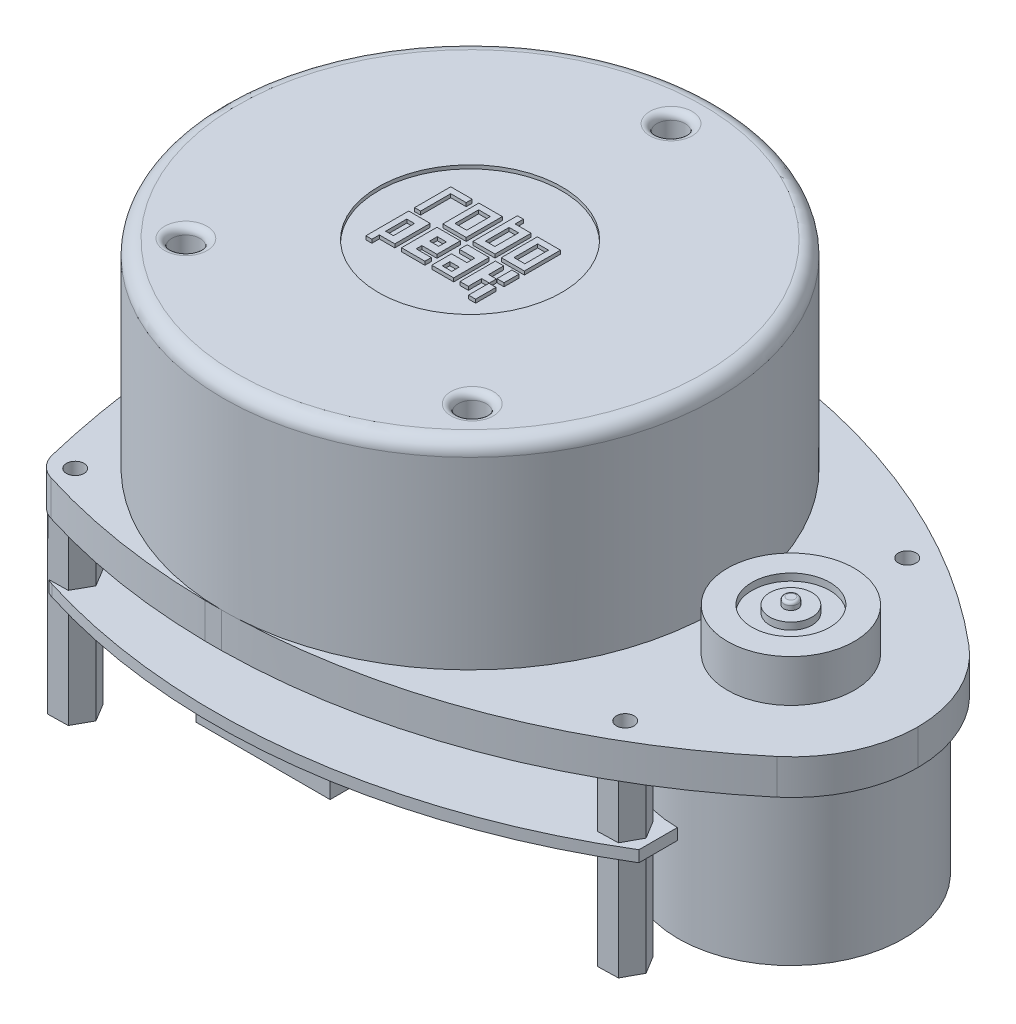
SolidWorks part; units mm, degrees
ref_plane "Спереди" through (0, 0, 0) normal (0, 0, 1) x (1, 0, 0)
ref_plane "Сверху" through (0, 0, 0) normal (0, 1, 0) x (1, 0, 0)
ref_plane "Справа" through (0, 0, 0) normal (1, 0, 0) x (0, 0, -1)
sketch "Эскиз1" plane through (0, 0, 0) normal (0, 1, 0) x (1, 0, 0)
  line L1 (-49.25, 35) -> (49.25, 35)
  line L2 (-49.25, 35) -> (-49.25, -35)
  line L3 (-49.25, -35) -> (49.25, -35)
  line L4 (49.25, 35) -> (49.25, -35)
  line L5 (-49.25, 35) -> (49.25, -35) construction
  line L6 (-49.25, -35) -> (49.25, 35) construction
  point P0 (0, 0)
  dimension "D1" = 98.5
  dimension "D2" = 70
extrude "Бобышка-Вытянуть1" add sketch "Эскиз1" along normal blind 5
sketch "Эскиз2" plane through (0, 5, 0) normal (0, 1, 0) x (1, 0, 0)
  line L0 (-49.25, 35) -> (-49.25, -35) construction
  circle A0 centre (-14.25, 0) radius 35
  point P2 (-49.25, 0)
  point P3 (-49.25, 0)
extrude "Бобышка-Вытянуть2" add sketch "Эскиз2" along normal blind 28.1
sketch "Эскиз3" plane through (0, 33.1, 0) normal (0, 1, 0) x (1, 0, 0)
  line L0 (-14.25, 0) -> (-14.25, 50000) construction
  line L1 (-14.25, -20) -> (-26.2883, -20) construction
  line L2 (-49.25, -35) -> (-14.25, -35) construction
  circle A0 centre (-14.25, 28.5) radius 2
  circle A1 centre (-34.5539, -20) radius 2
  circle A2 centre (6.0539, -20) radius 2
  arc A3 (-49.25, 0) -> (-14.25, -35) centre (-14.25, 0) ccw construction
  circle A4 centre (-14.25, 0) radius 35 construction
  dimension "D2" = 4
  dimension "D1" = 6.5
  dimension "D3" = 15
  dimension "D4" = 28.5
  dimension "D5" = 28.5
extrude "Вырез-Вытянуть1" cut sketch "Эскиз3" against normal blind 5
fillet "Скругление1" radius 2 1 edges at (-14.25, 33.1, 35)
fillet "Скругление2" radius 1 3 edges at (6.0539, 33.1, 22) (-34.5539, 33.1, 22) (-14.25, 33.1, -26.5)
sketch "Эскиз4" plane through (0, 33.1, 0) normal (0, 1, 0) x (1, 0, 0)
  line L0 (-22.1152, -6.9149) -> (-22.1152, -0.8316)
  line L1 (-22.1152, -0.8316) -> (-19.0735, -0.8316)
  line L2 (-19.0735, -0.8316) -> (-19.0735, -5.8538)
  line L3 (-19.0735, -5.8538) -> (-21.2663, -5.8538)
  line L4 (-21.2663, -5.8538) -> (-21.2663, -6.9149)
  line L5 (-21.2663, -6.9149) -> (-22.1152, -6.9149)
  line L6 (-22.1152, 0) -> (-22.1152, 5.1201)
  line L7 (-22.1152, 5.1201) -> (-19.0735, 5.1201)
  line L8 (-19.0735, 5.1201) -> (-19.0735, 4.2707)
  line L9 (-19.0735, 4.2707) -> (-21.2663, 4.2707)
  line L10 (-21.2663, 4.2707) -> (-21.2663, 0)
  line L11 (-21.2663, 0) -> (-22.1152, 0)
  line L12 (-21.2663, -1.9579) -> (-20.1699, -1.9579)
  line L13 (-20.1699, -1.9579) -> (-20.1699, -4.9509)
  line L14 (-20.1699, -4.9509) -> (-21.2663, -4.9509)
  line L15 (-21.2663, -4.9509) -> (-21.2663, -1.9579)
  line L16 (-13.8296, 0) -> (-13.8296, 6.293)
  line L17 (-18.1168, 0) -> (-14.8003, 0)
  line L18 (-18.1168, 0) -> (-18.1168, 5.1201)
  line L19 (-18.1168, 5.1201) -> (-14.8003, 5.1201)
  line L20 (-14.8003, 0) -> (-14.8003, 5.1201)
  line L21 (-9.8255, 5.1201) -> (-6.5494, 5.1201)
  line L22 (-9.8255, 5.1201) -> (-9.8255, 0)
  line L23 (-9.8255, 0) -> (-6.5494, 0)
  line L24 (-6.5494, 5.1201) -> (-6.5494, 0)
  line L25 (-8.9357, 4.2707) -> (-7.3988, 4.2707)
  line L26 (-8.9357, 4.2707) -> (-8.9357, 0.9137)
  line L27 (-8.9357, 0.9137) -> (-7.3988, 0.9137)
  line L28 (-7.3988, 4.2707) -> (-7.3988, 0.9137)
  line L29 (-17.3079, 4.2707) -> (-15.6497, 4.2707)
  line L30 (-17.3079, 4.2707) -> (-17.3079, 0.9137)
  line L31 (-17.3079, 0.9137) -> (-15.6497, 0.9137)
  line L32 (-15.6497, 4.2707) -> (-15.6497, 0.9137)
  line L33 (-12.9802, 4.2707) -> (-11.6455, 4.2707)
  line L34 (-12.9802, 4.2707) -> (-12.9802, 0.9137)
  line L35 (-12.9802, 0.9137) -> (-11.6455, 0.9137)
  line L36 (-11.6455, 4.2707) -> (-11.6455, 0.9137)
  line L37 (-12.9802, -4.142) -> (-11.6455, -4.142)
  line L38 (-12.9802, -4.142) -> (-12.9802, -5.1936)
  line L39 (-12.9802, -5.1936) -> (-11.6455, -5.1936)
  line L40 (-11.6455, -4.142) -> (-11.6455, -5.1936)
  line L41 (-16.9439, -1.9579) -> (-15.6497, -1.9579)
  line L42 (-16.9439, -1.9579) -> (-16.9439, -3.0499)
  line L43 (-16.9439, -3.0499) -> (-15.6497, -3.0499)
  line L44 (-15.6497, -1.9579) -> (-15.6497, -3.0499)
  line L46 (-7.5508, -0.7643) -> (-6.5494, -0.7643)
  line L47 (-7.5508, -0.7643) -> (-7.5508, -2.8858)
  line L48 (-7.5508, -2.8858) -> (-6.5494, -2.8858)
  line L49 (-6.5494, -0.7643) -> (-6.5494, -2.8858)
  line L50 (-6.5494, -6.9149) -> (-7.5508, -6.9149)
  line L51 (-6.5494, -6.9149) -> (-6.5494, -4.0216)
  line L52 (-6.5494, -4.0216) -> (-7.5508, -4.0216)
  line L53 (-13.8296, 6.293) -> (-12.9802, 6.293)
  line L54 (-12.9802, 6.293) -> (-12.9802, 5.1201)
  line L55 (-12.9802, 5.1201) -> (-10.7153, 5.1201)
  line L56 (-10.7153, 5.1201) -> (-10.7153, 0)
  line L57 (-10.7153, 0) -> (-13.8296, 0)
  line L58 (-9.8255, -0.8316) -> (-8.6437, -0.8316)
  line L59 (-8.6437, -0.8316) -> (-8.6437, -2.9608)
  line L60 (-8.6437, -2.9608) -> (-7.5508, -2.9608)
  line L61 (-9.8255, -0.8316) -> (-9.8255, -5.8538)
  line L62 (-9.8255, -5.8538) -> (-8.6437, -5.8538)
  line L63 (-8.6437, -5.8538) -> (-8.6437, -3.9573)
  line L64 (-8.6437, -3.9573) -> (-7.5508, -3.9573)
  line L65 (-7.5508, -2.9608) -> (-7.5508, -3.9573)
  line L66 (-13.8296, -0.8316) -> (-10.7153, -0.8316)
  line L67 (-10.7153, -0.8316) -> (-10.7153, -5.8538)
  line L68 (-10.7153, -5.8538) -> (-13.8296, -5.8538)
  line L69 (-13.8296, -5.8538) -> (-13.8296, -3.0499)
  line L70 (-13.8296, -3.0499) -> (-11.6455, -3.0499)
  line L71 (-11.6455, -3.0499) -> (-11.6455, -1.9408)
  line L72 (-11.6455, -1.9408) -> (-13.8296, -1.9408)
  line L73 (-13.8296, -1.9408) -> (-13.8296, -0.8316)
  line L74 (-18.1168, -0.8316) -> (-14.8003, -0.8316)
  line L75 (-14.8003, -0.8316) -> (-14.8003, -4.142)
  line L76 (-14.8003, -4.142) -> (-16.9439, -4.142)
  line L77 (-16.9439, -4.142) -> (-16.9439, -4.9509)
  line L78 (-16.9439, -4.9509) -> (-14.8003, -4.9509)
  line L79 (-14.8003, -4.9509) -> (-14.8003, -5.8538)
  line L80 (-14.8003, -5.8538) -> (-18.1168, -5.8538)
  line L81 (-18.1168, -5.8538) -> (-18.1168, -0.8316)
  line L82 (-7.5508, -6.9149) -> (-7.5508, -4.0216)
  circle A0 centre (-14.25, 0) radius 13
  dimension "D1" = 26
extrude "Вырез-Вытянуть3" cut sketch "Эскиз4" against normal blind 0.5 contours A0 L50 L82 L52 L51 L72 L73 L66 L67 L68 L69 L70 L71 L56 L57 L16 L53 L54 L55 L10 L11 L6 L7 L8 L9 L4 L5 L0 L1 L2 L3 L20 L17 L18 L19 L21 L24 L23 L22 L46 L49 L48 L47 | L32 L29 L30 L31 | L36 L33 L34 L35 | L28 L25 L26 L27 | L44 L41 L42 L43 | L15 L14 L13 L12 | L37 L40 L39 L38 region at (-20.7181, 33.1, 3.4544) region at (-8.1672, 33.1, -2.5922) region at (-16.4788, 33.1, -2.5922) region at (-12.3129, 33.1, -2.5922) region at (-16.2968, 33.1, 2.5039) region at (-14.2871, 33.1, -0.0991)
sketch "Эскиз5" plane through (0, 5, 0) normal (0, 1, 0) x (1, 0, 0)
  line L0 (-42.25, 30.7255) -> (-42.25, -39.5827) construction
  line L1 (27.75, 26.9972) -> (27.75, -49973.0028) construction
  line L2 (-49.25, 0) -> (49950.75, 0) construction
  circle A0 centre (-14.25, 0) radius 33 construction
  circle A1 centre (-42.25, 28) radius 1.25
  circle A2 centre (27.75, 20) radius 1.25
  circle A3 centre (27.75, -20) radius 1.25
  circle A4 centre (-42.25, -28) radius 1.25
  point P4 (-14.25, 33)
  dimension "D1" = 28
  dimension "D3" = 2.5
  dimension "D2" = 42
  dimension "D4" = 28
  dimension "D5" = 20
extrude "Вырез-Вытянуть4" cut sketch "Эскиз5" against normal blind 5
sketch "Эскиз6" plane through (0, 5, 0) normal (0, 1, 0) x (1, 0, 0)
  line L0 (49.25, 0) -> (50049.25, 0) construction
  line L1 (49.25, -35) -> (49.25, 35) construction
  circle A0 centre (31.25, 0) radius 9
  arc A1 (-14.25, -35) -> (-14.25, 35) centre (-14.25, 0) ccw construction
  point P4 (49.25, 0)
  dimension "D1" = 18
  dimension "D2" = 45.5
extrude "Бобышка-Вытянуть3" add sketch "Эскиз6" along normal blind 7
sketch "Эскиз7" plane through (0, 12, 0) normal (0, 1, 0) x (1, 0, 0)
  circle A0 centre (31.25, 0) radius 9
  circle A1 centre (31.25, 0) radius 0.9935
extrude "Вырез-Вытянуть5" cut sketch "Эскиз7" against normal blind 1
sketch "Эскиз8" plane through (0, 11, 0) normal (0, 1, 0) x (1, 0, 0)
  circle A0 centre (31.25, 0) radius 3.0011
  circle A1 centre (31.25, 0) radius 5.5217
extrude "Вырез-Вытянуть6" cut sketch "Эскиз8" against normal blind 1
fillet "Скругление3" radius 0.4 1 edges at (31.25, 12, 0.9935)
sketch "Эскиз9" plane through (0, 5, 0) normal (0, 1, 0) x (1, 0, 0)
  circle A0 centre (31.25, 0) radius 16
  dimension "D1" = 32
extrude "Бобышка-Вытянуть4" add sketch "Эскиз9" against normal blind 27
sketch "Эскиз10" plane through (0, 0, 0) normal (0, -1, 0) x (1, 0, 0)
  line L0 (-49.25, 0) -> (49950.75, 0) construction
  line L1 (-40.8546, 25.4729) -> (-39.3638, 27.9449)
  line L2 (-39.3638, 27.9449) -> (-40.7592, 30.472)
  line L3 (-40.7592, 30.472) -> (-43.6454, 30.5271)
  line L4 (-43.6454, 30.5271) -> (-45.1362, 28.0551)
  line L5 (-45.1362, 28.0551) -> (-43.7408, 25.528)
  line L6 (-43.7408, 25.528) -> (-40.8546, 25.4729)
  line L7 (29.2571, 22.4621) -> (26.3713, 22.5363)
  line L8 (26.3713, 22.5363) -> (24.8642, 20.0742)
  line L9 (24.8642, 20.0742) -> (26.2429, 17.5379)
  line L10 (26.2429, 17.5379) -> (29.1287, 17.4637)
  line L11 (29.1287, 17.4637) -> (30.6358, 19.9258)
  line L12 (30.6358, 19.9258) -> (29.2571, 22.4621)
  line L13 (30.6358, -19.9258) -> (29.2571, -22.4621)
  line L14 (29.1287, -17.4637) -> (30.6358, -19.9258)
  line L15 (26.2429, -17.5379) -> (29.1287, -17.4637)
  line L16 (24.8642, -20.0742) -> (26.2429, -17.5379)
  line L17 (26.3713, -22.5363) -> (24.8642, -20.0742)
  line L18 (29.2571, -22.4621) -> (26.3713, -22.5363)
  line L19 (-43.7408, -25.528) -> (-40.8546, -25.4729)
  line L20 (-45.1362, -28.0551) -> (-43.7408, -25.528)
  line L21 (-43.6454, -30.5271) -> (-45.1362, -28.0551)
  line L22 (-40.7592, -30.472) -> (-43.6454, -30.5271)
  line L23 (-39.3638, -27.9449) -> (-40.7592, -30.472)
  line L24 (-40.8546, -25.4729) -> (-39.3638, -27.9449)
  circle A0 centre (-42.25, 28) radius 2.5 construction
  circle A1 centre (27.75, 20) radius 2.5 construction
  circle A2 centre (27.75, -20) radius 2.5 construction
  circle A3 centre (-42.25, -28) radius 2.5 construction
  point P17 (27.75, 20)
  dimension "D1" = 5
  dimension "D2" = 5
extrude "Бобышка-Вытянуть5" add sketch "Эскиз10" along normal blind 24.6
sketch "Эскиз11" plane through (0, 5, 0) normal (0, 1, 0) x (1, 0, 0)
  circle A0 centre (-14.25, 0) radius 26
  dimension "D1" = 52
extrude "Бобышка-Вытянуть6" add sketch "Эскиз11" against normal blind 8
fillet "Скругление4" radius 1 1 edges at (-14.25, -3, 26)
sketch "Эскиз12" plane through (0, 5, 0) normal (0, 1, 0) x (1, 0, 0)
  line L1 (49.25, -35) -> (49.25, 35) construction
  line L2 (-49.25, 0) -> (-50049.25, 0) construction
  line L4 (-54.0511, 37.7308) -> (52.2004, 37.7308)
  line L5 (-54.0511, 37.7308) -> (-54.0511, -37.8351)
  line L6 (-54.0511, -37.8351) -> (52.2004, -37.8351)
  line L7 (52.2004, 37.7308) -> (52.2004, -37.8351)
  arc A0 (-49.25, 0) -> (-45.5286, 27.9743) centre (86.6751, -3.8473) cw
  circle A1 centre (-14.25, 0) radius 35 construction
  arc A3 (49.25, 0) -> (42.909, 13.5993) centre (31.4018, -0.0442) ccw
  arc A4 (-49.25, 0) -> (-14.25, -35) centre (-14.25, 0) ccw construction
  arc A5 (-42.835, 30.8555) -> (42.909, 13.5993) centre (-15.6796, -55.8665) cw
  arc A6 (-45.5286, 27.9743) -> (-42.835, 30.8555) centre (-41.6397, 27.0383) cw
  arc A7 (-45.5286, -27.9743) -> (-42.835, -30.8555) centre (-41.6397, -27.0383) ccw
  arc A8 (-42.835, -30.8555) -> (42.909, -13.5993) centre (-15.6796, 55.8665) ccw
  arc A9 (49.25, 0) -> (42.909, -13.5993) centre (31.4018, 0.0442) cw
  arc A10 (-49.25, 0) -> (-45.5286, -27.9743) centre (86.6751, 3.8473) ccw
  dimension "D1" = 4
extrude "Вырез-Вытянуть7" cut sketch "Эскиз12" against normal blind 8
fillet "Скругление5" radius 100 1 edges at (-49.25, 2.5, 0)
sketch "Эскиз13" plane through (0, 0, 0) normal (0, -1, 0) x (1, 0, 0)
  line L0 (31.5536, 21.8603) -> (31.5536, 16.4)
  line L1 (31.5536, -16.4) -> (31.5536, -21.8603)
  arc A0 (-49.0982, 0) -> (-45.3768, 27.9743) centre (86.8269, -3.8473) cw
  arc A1 (31.5536, 16.4) -> (31.5536, -16.4) centre (31.5536, 0) ccw
  arc A2 (-42.6831, 30.8555) -> (31.5536, 21.8603) centre (-15.5278, -55.8665) cw
  arc A3 (-45.3768, 27.9743) -> (-42.6831, 30.8555) centre (-41.4878, 27.0383) cw
  arc A4 (-45.3768, -27.9743) -> (-42.6831, -30.8555) centre (-41.4878, -27.0383) ccw
  arc A5 (-42.6831, -30.8555) -> (31.5536, -21.8603) centre (-15.5278, 55.8665) ccw
  arc A7 (-49.0982, 0) -> (-45.3768, -27.9743) centre (86.8269, 3.8473) ccw
  arc A8 (-48.5248, 10.6929) -> (-48.5248, -10.6929) centre (50.9018, 0) ccw construction
  point P16 (-49.0982, 0)
  point P21 (-49.0982, 0)
  dimension "D1" = 4
  dimension "D2" = 32.8
extrude "Бобышка-Вытянуть7" add sketch "Эскиз13" along normal blind 1.6 from offset 8
sketch "Эскиз14" plane through (0, -9.6, 0) normal (0, -1, 0) x (1, 0, 0)
  line L1 (-24.0982, 30) -> (-4.0982, 30)
  line L2 (-24.0982, 30) -> (-24.0982, 25)
  line L3 (-24.0982, 25) -> (-4.0982, 25)
  line L4 (-4.0982, 30) -> (-4.0982, 25)
  circle A0 centre (-14.25, 0) radius 35 construction
  point P4 (-14.0982, 30)
  dimension "D1" = 5
  dimension "D2" = 20
  dimension "D3" = 35
  dimension "D4" = 30
extrude "Бобышка-Вытянуть8" add sketch "Эскиз14" along normal blind 6
chamfer "Фаска1" distance 1 angle 45 1 edges at (-24.0982, -12.6, 30)
sketch "草圖1" plane through (0, -24.6, 0) normal (0, -1, 0) x (1, 0, 0)
  line L0 (29.2571, 22.4621) -> (26.2429, 17.5379) construction
  line L1 (26.2429, 17.5379) -> (26.3713, 22.5363) construction
  line L2 (26.3713, 22.5363) -> (29.1287, 17.4637) construction
  line L3 (26.2429, -17.5379) -> (29.2571, -22.4621) construction
  line L4 (29.2571, -22.4621) -> (29.1287, -17.4637) construction
  line L5 (29.1287, -17.4637) -> (26.2429, -17.5379) construction
  line L6 (29.1287, -17.4637) -> (26.2429, -17.5379) construction
  line L7 (29.1287, -17.4637) -> (26.3713, -22.5363) construction
  line L8 (24.8642, -20.0742) -> (26.3713, -22.5363) construction
  line L9 (26.3713, -22.5363) -> (29.2571, -22.4621) construction
  circle A0 centre (27.75, 20) radius 1.5
  circle A1 centre (27.75, -20) radius 1.5
  dimension "D1" = 3
  dimension "D2" = 3
extrude "除料-伸長1" cut sketch "草圖1" against normal blind 10
